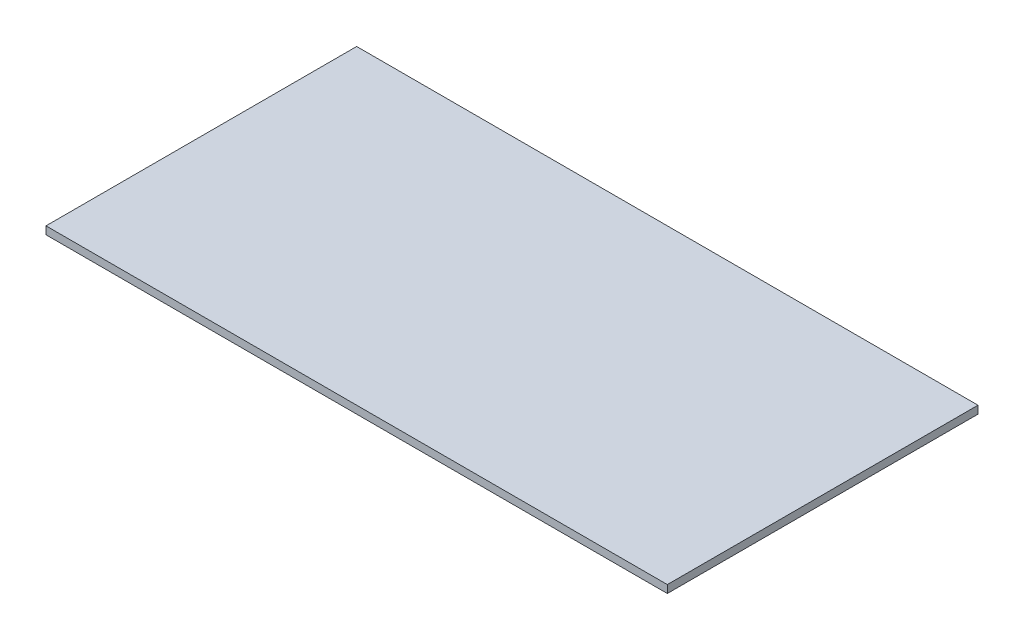
SolidWorks part; units mm, degrees
material "Balsa"
ref_plane "Front Plane" through (0, 0, 0) normal (0, 0, 1) x (1, 0, 0)
ref_plane "Top Plane" through (0, 0, 0) normal (0, 1, 0) x (1, 0, 0)
ref_plane "Right Plane" through (0, 0, 0) normal (1, 0, 0) x (0, 0, -1)
sketch "Sketch1" plane through (0, 0, 0) normal (0, 1, 0) x (1, 0, 0)
  line L1 (-200, -100) -> (200, -100)
  line L2 (-200, -100) -> (-200, 100)
  line L3 (-200, 100) -> (200, 100)
  line L4 (200, -100) -> (200, 100)
  line L5 (-200, -100) -> (200, 100) construction
  line L6 (-200, 100) -> (200, -100) construction
  point P0 (0, 0)
  dimension "D1" = 200
  dimension "D2" = 400
extrude "Boss-Extrude1" add sketch "Sketch1" along normal blind 5
